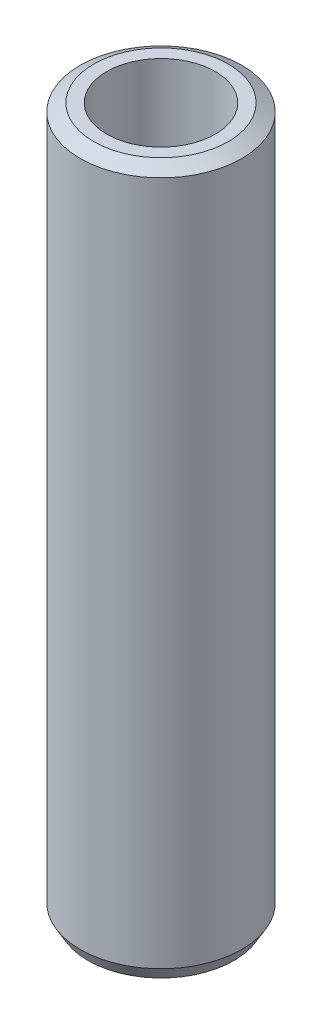
SolidWorks part; units mm, degrees
ref_plane "Front Plane" through (0, 0, 0) normal (0, 0, 1) x (1, 0, 0)
ref_plane "Top Plane" through (0, 0, 0) normal (0, 1, 0) x (1, 0, 0)
ref_plane "Right Plane" through (0, 0, 0) normal (1, 0, 0) x (0, 0, -1)
sketch "Sketch1" plane through (0, 0, 0) normal (0, 1, 0) x (1, 0, 0)
  circle A0 centre (0, 0) radius 12.5
  dimension "SHAFT_OD" = 25
extrude "Boss-Extrude1" add sketch "Sketch1" along normal blind 109.2493
sketch "Sketch2" plane through (0, 0, 0) normal (0, 1, 0) x (1, 0, 0)
  circle A0 centre (0, 0) radius 8.3956
  dimension "BORE_D" = 16.7911
extrude "Cut-Extrude1" cut sketch "Sketch2" along normal through all
chamfer "Chamfer1" distance 1.2105 angle 60 2 edges at (0, 109.2493, 12.5) (0, 0, 12.5) first distance on face at (0, 109.2493, 12.5) first distance on face at (0, 0, 8.3956)
